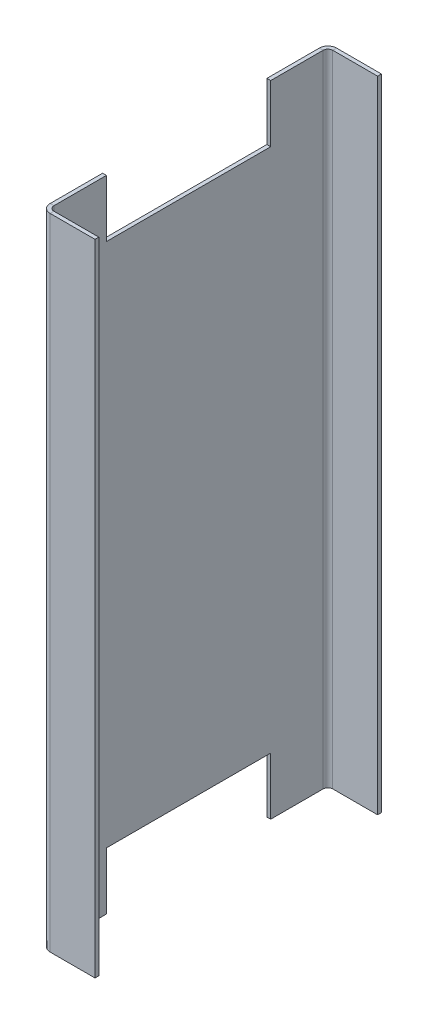
SolidWorks part; units mm, degrees
note: The reader was unsure of these and kept them because the rebuilt part matched: flange length of "Edge-Flange1".
material "AISI 304"
ref_plane "Front" through (0, 0, 0) normal (0, 0, 1) x (1, 0, 0)
ref_plane "Top" through (0, 0, 0) normal (0, 1, 0) x (1, 0, 0)
ref_plane "Right" through (0, 0, 0) normal (1, 0, 0) x (0, 0, -1)
sketch "Sketch1" plane through (0, 0, 0) normal (1, 0, 0) x (0, 0, -1)
  line L1 (-75, -167.5) -> (75, -167.5)
  line L2 (-75, -167.5) -> (-75, 167.5)
  line L3 (-75, 167.5) -> (75, 167.5)
  line L4 (75, -167.5) -> (75, 167.5)
  line L5 (-75, -167.5) -> (75, 167.5) construction
  line L6 (-75, 167.5) -> (75, -167.5) construction
  point P0 (0, 0)
  dimension "D1" = 150
  dimension "D2" = 335
base flange "Base-Flange1" sketch "Sketch1" thickness 2 reverse thickness direction no parameters "D1"=8
edge flange "Edge-Flange1" sketch "Sketch8" flange profiles "Sketch8", "Sketch10" flange angle 90 flange length 28 flange position material inside bend radius 2.5 thickness 2 relief rectangular parameters "D6"=10, "D8"=1
sketch "Sketch8" plane through (0, 0, -75) normal (0, 0, -1) x (0, 1, 0)
  line L2 (-167.5, 0) -> (-167.5, 26)
  line L3 (-167.5, 26) -> (167.5, 26)
  line L4 (167.5, 26) -> (167.5, 0)
  line L7 (-167.5, 0) -> (167.5, 0) construction
  line L8 (-167.5, 0) -> (167.5, 0)
sketch "Sketch10" plane through (0, 0, 75) normal (0, 0, 1) x (0, -1, 0)
  line L0 (-167.5, 0) -> (167.5, 0) construction
  line L1 (-167.5, 0) -> (167.5, 0)
  line L2 (-167.5, 0) -> (-167.5, 26)
  line L3 (-167.5, 26) -> (167.5, 26)
  line L4 (167.5, 26) -> (167.5, 0)
bend "EdgeBend1" bend radius 2.5 bend angle 90 parameters "D5"=1
bend "EdgeBend2" bend radius 2.5 bend angle 90 parameters "D5"=3
sketch "Sketch11" plane through (0, 0, 0) normal (1, 0, 0) x (0, 0, -1)
  line L0 (-75, 167.5) -> (75, 167.5) construction
  line L1 (-43, 167.5) -> (43, 167.5)
  line L2 (-43, 167.5) -> (-43, 137.5)
  line L3 (-43, 137.5) -> (43, 137.5)
  line L4 (43, 167.5) -> (43, 137.5)
  line L5 (73, 167.5) -> (73, -167.5) construction
  point P6 (0, 167.5)
  dimension "D1" = 30
  dimension "D2" = 30
extrude "Cut-Extrude1" cut sketch "Sketch11" against normal blind 10 normal cut yes
mirror "Mirror1" about plane through (0, 0, 0) normal (0, 1, 0) of "Cut-Extrude1"
sketch "Bend-Lines1" [suppressed] plane through (0, 0, 0) normal (0, 1, 0) x (1, 0, 0)
sketch "Bounding-Box1" [suppressed] plane through (0, 0, 0) normal (0, 1, 0) x (1, 0, 0)
sheet metal parameters "Sheet-Metal1" thickness 2 parameters "D1"=8
flat pattern "Flat-Pattern1" [suppressed]
sketch "Bend-Lines2" plane through (0, 0, 0) normal (0, 1, 0) x (1, 0, 0)
sketch3d "Bounding-Box2" [suppressed]
  line L0 (15, 191, 0) -> (15, -191, 0) construction
  line L1 (-15, 191, 0) -> (-15, -191, 0) construction
  line L2 (15, 191, 0) -> (-15, 191, 0) construction
  line L3 (15, -191, 0) -> (-15, -191, 0) construction
sheet metal parameters "Sheet-Metal2" thickness 2 parameters "D1"=8
flat pattern "Flat-Pattern1"
sketch "Bend-Lines2" plane through (0, 0, 0) normal (1, 0, 0) x (0, 0, -1)
  line L0 (73.2489, -137.5) -> (73.2489, 137.5) construction
  line L1 (73.2489, -137.5) -> (73.2489, 137.5) construction
  line L2 (-73.2489, 137.5) -> (-73.2489, -137.5) construction
  line L3 (-73.2489, 137.5) -> (-73.2489, -137.5) construction
sketch3d "Bounding-Box2" [suppressed]
  line L0 (-99.4978, 137.5, 0) -> (-99.4978, -137.5, 0) construction
  line L1 (99.4978, 137.5, 0) -> (99.4978, -137.5, 0) construction
  line L2 (-99.4978, 137.5, 0) -> (99.4978, 137.5, 0) construction
  line L3 (-99.4978, -137.5, 0) -> (99.4978, -137.5, 0) construction
bend of the flat pattern "Flatten-<EdgeBend1>1"
bend of the flat pattern "Flatten-<EdgeBend2>1"
sheet metal parameters "Sheet-Metal3" thickness 2 parameters "D1"=8
flat pattern "Flat-Pattern1"
sketch "Bend-Lines2" plane through (0, 0, 0) normal (1, 0, 0) x (0, 0, -1)
  line L0 (73.2489, -137.5) -> (73.2489, 137.5) construction
  line L1 (73.2489, -137.5) -> (73.2489, 137.5) construction
  line L2 (-73.2489, 137.5) -> (-73.2489, -137.5) construction
  line L3 (-73.2489, 137.5) -> (-73.2489, -137.5) construction
sketch3d "Bounding-Box2" [suppressed]
  line L0 (-99.4978, 137.5, 0) -> (-99.4978, -137.5, 0) construction
  line L1 (99.4978, 137.5, 0) -> (99.4978, -137.5, 0) construction
  line L2 (-99.4978, 137.5, 0) -> (99.4978, 137.5, 0) construction
  line L3 (-99.4978, -137.5, 0) -> (99.4978, -137.5, 0) construction
bend of the flat pattern "Flatten-<EdgeBend1>1"
bend of the flat pattern "Flatten-<EdgeBend2>1"
sheet metal parameters "Sheet-Metal4" thickness 2 parameters "D1"=8
flat pattern "Flat-Pattern1"
sketch "Bend-Lines2" plane through (0, 0, 0) normal (1, 0, 0) x (0, 0, -1)
  line L0 (73.2489, -167.5) -> (73.2489, 167.5) construction
  line L1 (73.2489, -167.5) -> (73.2489, 167.5) construction
  line L2 (-73.2489, 167.5) -> (-73.2489, -167.5) construction
  line L3 (-73.2489, 167.5) -> (-73.2489, -167.5) construction
sketch3d "Bounding-Box2" [suppressed]
  line L0 (-99.4978, 167.5, 0) -> (-99.4978, -167.5, 0) construction
  line L1 (99.4978, 167.5, 0) -> (99.4978, -167.5, 0) construction
  line L2 (-99.4978, 167.5, 0) -> (99.4978, 167.5, 0) construction
  line L3 (-99.4978, -167.5, 0) -> (99.4978, -167.5, 0) construction
bend of the flat pattern "Flatten-<EdgeBend1>1"
bend of the flat pattern "Flatten-<EdgeBend2>1"
